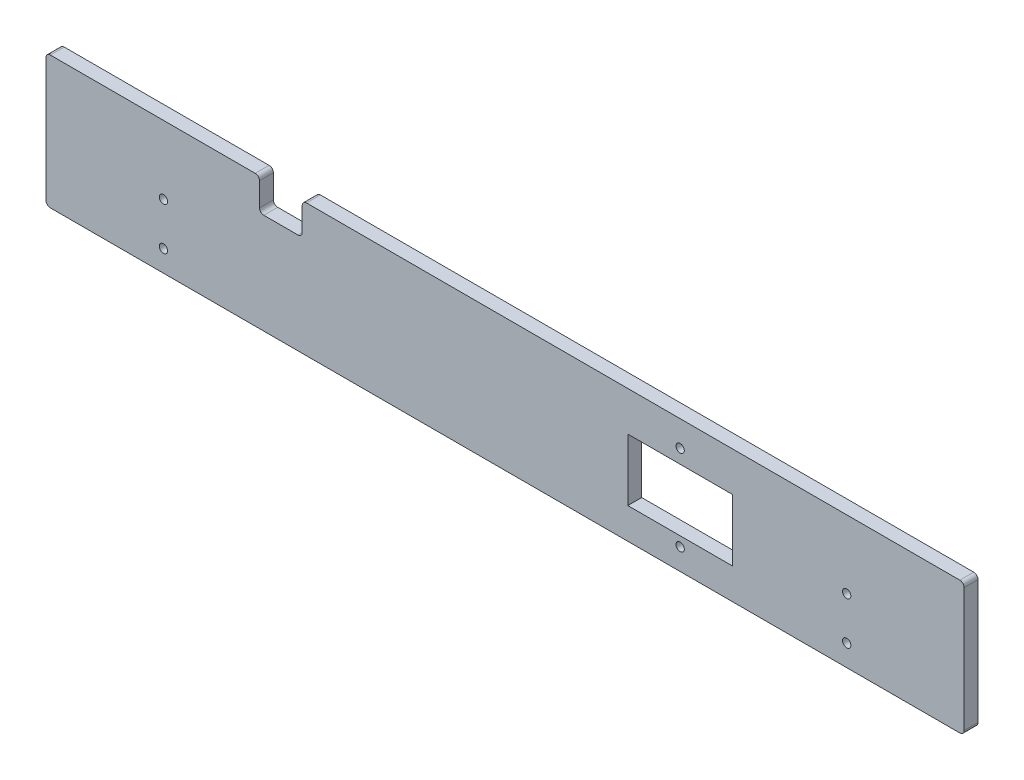
SolidWorks part; units mm, degrees
ref_plane "Front Plane" through (0, 0, 0) normal (0, 0, 1) x (1, 0, 0)
ref_plane "Top Plane" through (0, 0, 0) normal (0, 1, 0) x (1, 0, 0)
ref_plane "Right Plane" through (0, 0, 0) normal (1, 0, 0) x (0, 0, -1)
sketch "Sketch1" plane through (0, 0, 0) normal (0, 0, 1) x (1, 0, 0)
  line L0 (-231.9248, 29.7035) -> (78.0752, 29.7035)
  line L1 (-351.9248, 29.7035) -> (-251.9248, 29.7035)
  line L2 (-351.9248, 29.7035) -> (-351.9248, -32.2965)
  line L3 (-351.9248, -32.2965) -> (78.0752, -32.2965)
  line L4 (78.0752, 29.7035) -> (78.0752, -32.2965)
  line L5 (-79.4248, 11.2035) -> (-30.4248, 11.2035)
  line L6 (-79.4248, 11.2035) -> (-79.4248, -17.7965)
  line L7 (-79.4248, -17.7965) -> (-30.4248, -17.7965)
  line L8 (-30.4248, 11.2035) -> (-30.4248, -17.7965)
  line L10 (-231.9248, 29.7035) -> (-231.9248, 14.7035)
  line L11 (-231.9248, 14.7035) -> (-251.9248, 14.7035)
  line L12 (-251.9248, 29.7035) -> (-251.9248, 14.7035)
  circle A0 centre (-54.9248, 17.7035) radius 1.95
  circle A1 centre (-54.9248, -22.2965) radius 1.95
  point P12 (-54.9248, 11.2035)
  dimension "D3" = 133
  dimension "D4" = 40
  dimension "D1" = 430
  dimension "D2" = 62
  dimension "D5" = 10
  dimension "D6" = 49
  dimension "D7" = 29
  dimension "D8" = 6.5
  dimension "D9" = 20
  dimension "D10" = 100
  dimension "D11" = 15
extrude "Boss-Extrude1" add sketch "Sketch1" along normal blind 1.5 and the other way blind 5
fillet "Fillet1" radius 2 8 edges at (78.0752, -32.2965, -1.75) (-351.9248, -32.2965, -1.75) (-351.9248, 29.7035, -1.75) (-231.9248, 14.7035, -1.75) (-251.9248, 14.7035, -1.75) (-251.9248, 29.7035, -1.75) (-231.9248, 29.7035, -1.75) (78.0752, 29.7035, -1.75)
sketch "Sketch3" plane through (0, 0, -5) normal (0, 0, -1) x (-1, 0, 0)
  line L0 (349.9248, -32.2965) -> (-76.0752, -32.2965) construction
  line L1 (-78.0752, -30.2965) -> (-78.0752, 27.7035) construction
  line L2 (351.9248, 27.7035) -> (351.9248, -30.2965) construction
  circle A0 centre (-23.0752, -22.2965) radius 1.95
  circle A1 centre (-23.0752, -2.2965) radius 1.95
  circle A2 centre (296.9248, -22.2965) radius 1.95
  circle A3 centre (296.9248, -2.2965) radius 1.95
  dimension "D1" = 10
  dimension "D3" = 20
  dimension "D4" = 55
  dimension "D2" = 55
  dimension "D5" = 20
  dimension "D6" = 10
extrude "Cut-Extrude1" cut sketch "Sketch3" against normal blind 10
